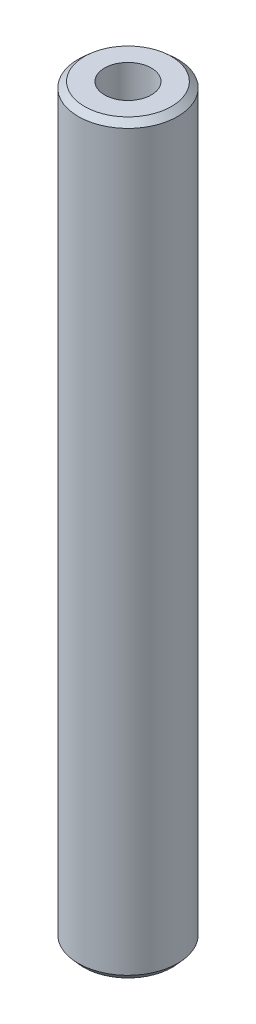
SolidWorks part; units mm, degrees
ref_plane "Front Plane" through (0, 0, 0) normal (0, 0, 1) x (1, 0, 0)
ref_plane "Top Plane" through (0, 0, 0) normal (0, 1, 0) x (1, 0, 0)
ref_plane "Right Plane" through (0, 0, 0) normal (1, 0, 0) x (0, 0, -1)
sketch "Sketch1" plane through (0, 0, 0) normal (0, 1, 0) x (1, 0, 0)
  circle A0 centre (0, 0) radius 40
  dimension "SHAFT_OD" = 80
extrude "Boss-Extrude1" add sketch "Sketch1" along normal blind 600
sketch "Sketch2" plane through (0, 0, 0) normal (0, 1, 0) x (1, 0, 0)
  circle A0 centre (0, 0) radius 18.8081
  dimension "BORE_D" = 37.6161
extrude "Cut-Extrude1" cut sketch "Sketch2" along normal through all
chamfer "Chamfer1" distance 4.4591 angle 48.458 2 edges at (0, 600, 40) (0, 0, 40) first distance on face at (0, 600, 40) first distance on face at (0, 0, 18.8081)
